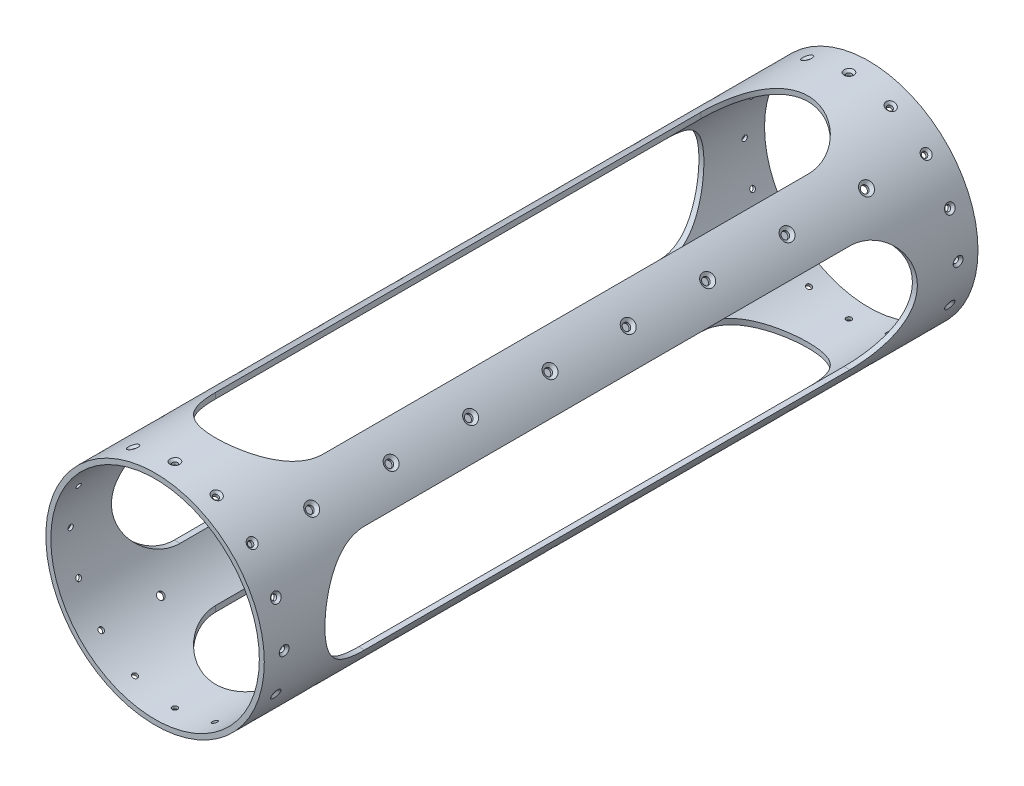
SolidWorks part; units mm, degrees
material "6061-T6 (SS)"
ref_plane "Front Plane" through (0, 0, 0) normal (0, 0, 1) x (1, 0, 0)
ref_plane "Top Plane" through (0, 0, 0) normal (0, 1, 0) x (1, 0, 0)
ref_plane "Right Plane" through (0, 0, 0) normal (1, 0, 0) x (0, 0, -1)
sketch "Sketch1" plane through (0, 0, 0) normal (0, 0, 1) x (1, 0, 0)
  circle A0 centre (0, 0) radius 66.675
  circle A1 centre (0, 0) radius 69.85
extrude "Extrude1" add sketch "Sketch1" along normal blind 228.2063
ref_plane "Plane2" through (0, 0, 215.5063) normal (0, 0, 1) x (1, 0, 0)
sketch "Sketch2" plane through (0, 0, 215.5063) normal (0, 0, 1) x (1, 0, 0)
  circle A0 centre (0, 0) radius 69.85 construction
  point P0 (0, -69.85)
ref_plane "Plane3" through (0, -69.85, 215.5063) normal (0, -1, 0) x (1, 0, 0)
hole_wizard "CSK for M3 Flat Head Machine Screw1" positions "Sketch4" profile "Sketch3" countersink size "M3" standard "Ansi Metric" end condition through all
sketch "Sketch4" plane through (0, -69.85, 215.5063) normal (0, -1, 0) x (1, 0, 0)
  point P1 (0, 0)
sketch "Sketch3" plane through (0, -69.85, 215.5063) normal (1, 0, 0) x (0, 0, -1)
  line L0 (0, 0) -> (0, 161.1134)
  line L1 (0, 161.1134) -> (1.7, 161.1134)
  line L2 (1.7, 161.1134) -> (1.7, 1.45)
  line L3 (1.7, 1.45) -> (3.15, 0)
  line L5 (3.15, 0) -> (0, 0)
  line L6 (-1.7, 1.45) -> (-3.15, 0) construction
  line L11 (0, -6.35) -> (0, 107.95) construction
  dimension "Thru Hole Dia." = 3.4
  dimension "Thru Hole Depth" = 161.1134
  dimension "Near C'Sink Dia." = 6.3
  dimension "Near C'Sink Angle" = 90
sketch "Sketch5" plane through (0, 0, 0) normal (0, 1, 0) x (1, 0, 0)
  line L0 (0, 0) -> (34.29, 0)
  line L1 (69.85, 0) -> (-69.85, 0) construction
  line L2 (0, 0) -> (-34.29, 0)
  line L3 (66.675, 0) -> (-66.675, 0) construction
  line L4 (-34.29, 0) -> (-34.29, -155.1392)
  line L5 (34.29, 0) -> (34.29, -155.1392)
  line L6 (-34.29, -155.1392) -> (34.29, -155.1392) construction
  arc A0 (-34.29, -155.1392) -> (34.29, -155.1392) centre (0, -155.1392) ccw
  dimension "D1" = 155.1392
extrude "Extrude2" cut sketch "Sketch5" against normal through all and the other way through all
pattern_circular "CirPattern2" count 4 over 360 about axis through (0, 0, 228.2063) along (0, 0, -1) of "Extrude2"
pattern_circular "CirPattern1" count 16 over 360 about axis through (0, 0, 228.2063) along (0, 0, -1) of "CSK for M3 Flat Head Machine Screw1"
ref_plane "Plane4" through (0, 0, 0) normal (0.7071, 0.7071, 0) x (0, 0, -1)
ref_plane "Plane5" through (49.3914, -49.3914, 114.1031) normal (0.7071, -0.7071, 0) x (-0.7071, -0.7071, 0)
sketch "Sketch10" plane through (49.3914, -49.3914, 114.1031) normal (0.7071, -0.7071, 0) x (-0.7071, -0.7071, 0)
  line L0 (0, -101.4032) -> (0, -63.3032) construction
hole_wizard "CSK for #8 Flat Head Machine Screw (100)1" positions "Sketch12" profile "Sketch11" countersink size "#8" standard "Ansi Inch" end condition through all
sketch "Sketch12" plane through (49.3914, -49.3914, 114.1031) normal (0.7071, -0.7071, 0) x (-0.7071, -0.7071, 0)
  point P1 (0, -63.3032)
sketch "Sketch11" plane through (49.3914, -49.3914, 177.4063) normal (0, 0, 1) x (0.7071, 0.7071, 0)
  line L0 (0, 0) -> (0, 168.6328)
  line L1 (0, 168.6328) -> (2.2479, 168.6328)
  line L2 (2.2479, 168.6328) -> (2.2479, 1.6518)
  line L3 (2.2479, 1.6518) -> (4.2164, 0)
  line L5 (4.2164, 0) -> (0, 0)
  line L6 (-2.2479, 1.6518) -> (-4.2164, 0) construction
  line L11 (0, -6.35) -> (0, 107.95) construction
  dimension "Thru Hole Dia." = 4.4958
  dimension "Thru Hole Depth" = 168.6328
  dimension "Near C'Sink Dia." = 8.4328
  dimension "Near C'Sink Angle" = 100
pattern_linear "LPattern1" count 4 spacing 50.8 along (0, 0, -1) of "CSK for #8 Flat Head Machine Screw (100)1"
pattern_circular "CirPattern3" count 4 over 360 about axis through (0, 0, 228.2063) along (0, 0, -1) of "LPattern1", "CSK for #8 Flat Head Machine Screw (100)1"
mirror "Mirror1" about plane through (0, 0, 0) normal (0, 0, 1) of "CirPattern3", "CSK for M3 Flat Head Machine Screw1", "CirPattern1", "Extrude1", "Extrude2", "CirPattern2", "CSK for #8 Flat Head Machine Screw (100)1", "LPattern1"
